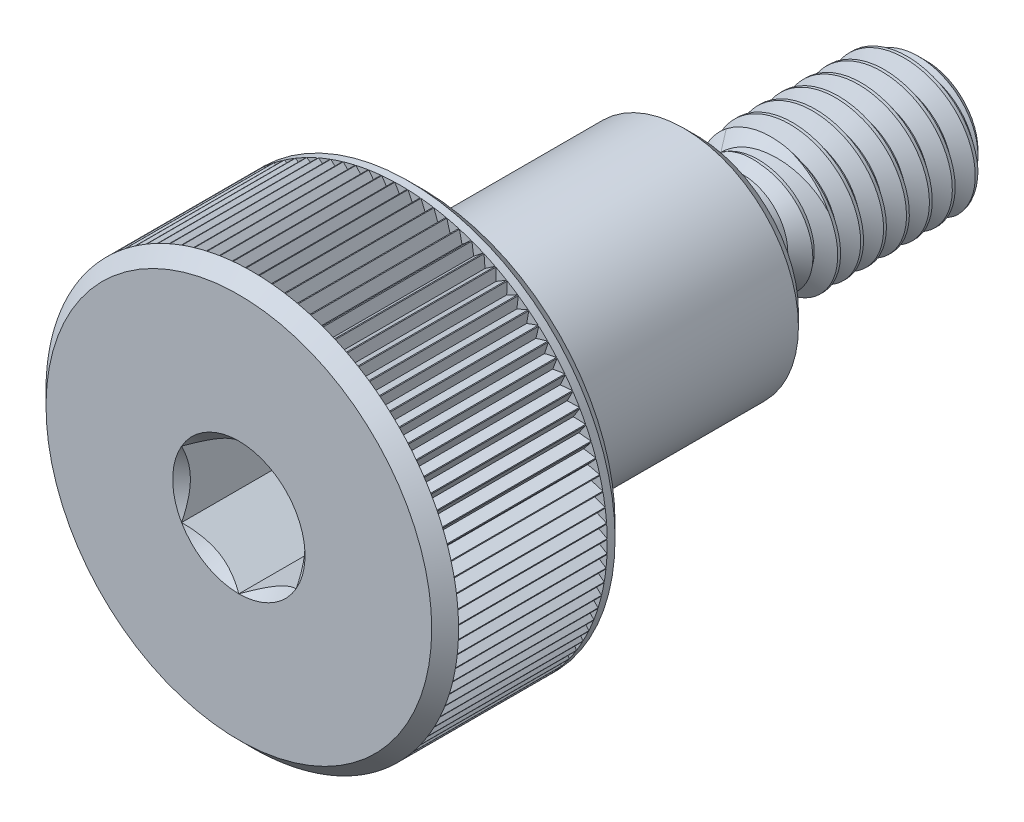
SolidWorks part; units mm, degrees
material "AISI 304"
ref_plane "Front Plane" through (0, 0, 0) normal (0, 0, 1) x (1, 0, 0)
ref_plane "Top Plane" through (0, 0, 0) normal (0, 1, 0) x (1, 0, 0)
ref_plane "Right Plane" through (0, 0, 0) normal (1, 0, 0) x (0, 0, -1)
sketch "Sketch1" plane through (0, 0, 0) normal (1, 0, 0) x (0, 0, -1)
  line L0 (-7.5, 0) -> (7.5, 0) construction
  line L1 (-7.5, -4.5) -> (-7.5, 4.5) construction
  line L2 (-7.5, 4.5) -> (-3.5, 4.5) construction
  line L3 (-3.5, 4.5) -> (-3.5, 2.297) construction
  line L4 (-3.5, 2.297) -> (-2.992, 2.297) construction
  line L5 (-2.992, 2.297) -> (-2.789, 2.5) construction
  line L6 (-2.789, 2.5) -> (2.5, 2.5) construction
  line L7 (7.4687, 1.5541) -> (7.7187, 1.1211) construction
  line L8 (7.7187, 1.1211) -> (7.9688, 1.5541) construction
  line L9 (7.5, -1.5) -> (7.5, 1.5) construction
  line L10 (2.5, 2.5) -> (7.5, 2.5) construction
  line L11 (7.9688, 1.5541) -> (7.4687, 1.5541) construction
  line L12 (7.7188, 1.5541) -> (7.7187, 1.5) construction
  line L13 (7.7187, 1.1211) -> (7.7187, 1.1752) construction
  line L14 (7.75, 1.1752) -> (7.6875, 1.1752) construction
  line L15 (7.9375, 1.5) -> (7.5, 1.5) construction
  line L16 (7.7187, 1.5271) -> (7.9531, 1.5271) construction
  line L17 (7.7187, 1.5271) -> (7.4844, 1.5271) construction
  line L18 (-7.5, 4.2075) -> (-7.2075, 4.5) construction
  line L19 (-3.7925, 4.5) -> (-3.5, 4.2075) construction
  line L20 (7.5, 1.5) -> (2.5, 1.5) construction
  line L21 (7.125, 1.5) -> (7.5, 1.125) construction
  line L22 (4.025, 1.5) -> (3.5, 0.975) construction
  line L23 (3.5, 0.975) -> (2.7625, 0.975) construction
  line L24 (2.5, 1.5) -> (2.5, 1.2375) construction
  line L25 (-5.5, 1.25) -> (-5.5, -1.25) construction
  line L26 (-5.5, -1.25) -> (-7.5, -1.25) construction
  line L27 (-5.5, 1.25) -> (-7.5, 1.25) construction
  line L28 (-7.2075, 0) -> (-3.9633, 0) construction
  arc A0 (2.5, 1.2375) -> (2.7625, 0.975) centre (2.7625, 1.2375) ccw construction
  point P4 (0, 0)
  point P7 (-7.5, 0)
  point P18 (7.5, 0)
  point P25 (5.75, -1.5)
  point P38 (-5.5, 4.5)
  point P45 (-5.5, 0)
  point P46 (3.7625, 1.2375)
  point P48 (-2.992, 0)
  point P51 (-5.5, 0)
  point P52 (2.5, 0)
  dimension "Head Diameter" = 9
  dimension "Head Height" = 4
  dimension "Thread Diameter" = 3
  dimension "Shoulder Diameter" = 5
  dimension "Thread Length" = 5
  dimension "D1" = 0.508
  dimension "D2" = 135
  dimension "D3" = 0.203
  dimension "Shoulder Length" = 6
  dimension "Thread Pitch" = 0.5
  dimension "D4" = 0.0625
  dimension "D5" = 1.75
  dimension "D6" = 0.2925
  dimension "D7" = 0.375
  dimension "D8" = 1.95
  dimension "D9" = 1
  dimension "Drive Size" = 2.5
  dimension "Knurling Length" = 3.2443
sketch "Sketch3" plane through (0, 0, 0) normal (1, 0, 0) x (0, 0, -1)
  line L0 (-7.5, 0) -> (-7.5, 4.2075)
  line L1 (-7.5, -4.5) -> (-7.5, 4.5) construction
  line L2 (-7.5, 4.2075) -> (-7.2075, 4.5)
  line L3 (-7.2075, 4.5) -> (-3.7925, 4.5)
  line L4 (-3.7925, 4.5) -> (-3.5, 4.2075)
  line L5 (-3.5, 4.2075) -> (-3.5, 2.297)
  line L6 (-3.5, 2.297) -> (-2.992, 2.297)
  line L7 (-2.992, 2.297) -> (-2.789, 2.5)
  line L8 (-2.789, 2.5) -> (2.5, 2.5)
  line L9 (2.5, 2.5) -> (2.5, 1.2375)
  line L10 (2.7625, 0.975) -> (3.5, 0.975)
  line L11 (3.5, 0.975) -> (4.025, 1.5)
  line L12 (4.025, 1.5) -> (7.125, 1.5)
  line L13 (7.125, 1.5) -> (7.5, 1.125)
  line L14 (7.5, 1.125) -> (7.5, 0)
  line L15 (7.5, 0) -> (-7.5, 0)
  arc A0 (2.5, 1.2375) -> (2.7625, 0.975) centre (2.7625, 1.2375) ccw construction
  arc A1 (2.5, 1.2375) -> (2.7625, 0.975) centre (2.7625, 1.2375) ccw
revolve "Revolve1" add sketch "Sketch3" angle 360 about L0
sketch "Sketch4" plane through (0, 0, 0) normal (0, 0, 1) x (1, 0, 0)
  line L0 (0, -4.5) -> (0, 4.5) construction
  line L1 (0, 1.4434) -> (-1.25, 0.7217)
  line L2 (-1.25, 0.7217) -> (-1.25, -0.7217)
  line L3 (-1.25, -0.7217) -> (0, -1.4434)
  line L4 (0, -1.4434) -> (1.25, -0.7217)
  line L5 (1.25, -0.7217) -> (1.25, 0.7217)
  line L6 (1.25, 0.7217) -> (0, 1.4434)
  circle A0 centre (0, 0) radius 1.25 construction
extrude "Cut-Extrude1" cut sketch "Sketch4" against normal up to vertex (-5.5 mm away) from vertex up to point (0, 0, 5.5) starting at point (0, 0, 7.5)
sketch "Sketch5" plane through (0, 0, 0) normal (0, 0, 1) x (1, 0, 0)
  line L0 (0, -4.5) -> (0, 4.5) construction
  circle A0 centre (0, 0) radius 1.4434
extrude "Cut-Extrude2" cut sketch "Sketch5" against normal up to vertex (-5.5 mm away) draft 45 from vertex up to point (0, 0, 5.5) starting at point (0, 0, 7.5)
chamfer "Chamfer1" distance 0.2925 angle 45 1 edges at (2.5, 0, -2.5)
sketch "Sketch6" plane through (0, 0, -7.5) normal (0, 0, -1) x (-1, 0, 0)
  circle A0 centre (0, 0) radius 1.5
curve "Helix/Spiral1" pitch 0.5 height 4.75 radius 1.5 centre (0, 0, -7.5) axis (0, 0, 1) start towards (0, 1, 0)
ref_plane "Plane1" through (0, 0, -3.5) normal (0, 0, 1) x (1, 0, 0)
split "Split1" trim tools "Plane1" bodies to split 106 resulting bodies 110 111
sketch "Sketch7" plane through (0, 0, 0) normal (1, 0, 0) x (0, 0, -1)
  line L0 (7.4844, 1.5271) -> (7.6875, 1.1752)
  line L1 (7.6875, 1.1752) -> (7.75, 1.1752)
  line L2 (7.75, 1.1752) -> (7.9531, 1.5271)
  line L3 (7.9531, 1.5271) -> (7.4844, 1.5271)
sweep "Cut-Sweep1" cut profiles "Sketch7" path "Helix/Spiral1" align with end faces yes
combine bodies "Combine1" operation type add bodies to combine 110 107
sketch "Sketch8" plane through (0, 0, 0) normal (0, 0, 1) x (1, 0, 0)
  line L0 (0, 4.5) -> (0, 0) construction
  line L1 (-0.1351, 4.5) -> (0.1351, 4.5)
  line L2 (0.1351, 4.5) -> (0, 4.266)
  line L3 (0, 4.266) -> (-0.1351, 4.5)
  line L4 (-0.1351, 4.5) -> (0, 0) construction
  line L5 (0, 0) -> (0.1351, 4.5) construction
  circle A0 centre (0, 0) radius 4.266 construction
  point P8 (0, 4.5)
  dimension "D1" = 0.234
  dimension "D2" = 3.439
extrude "Cut-Extrude3" cut sketch "Sketch8" against normal up to vertex (-3.9632 mm away) from vertex up to point (0, 0, 3.9633) starting at point (0, 0, 7.2075)
pattern_circular "CirPattern1" count 99 over 360 about axis through (0, 0, 7.5) along (0, 0, -1) of "Cut-Extrude3"
equation "\"D4@Sketch1\"=\"Thread Pitch@Sketch1\"/8"
equation "\"D5@Sketch1\"=\"Thread Pitch@Sketch1\"*3.5"
equation "\"D6@Sketch1\"=\"Head Diameter@Sketch1\"*.0325"
equation "\"D7@Sketch1\"=\"Thread Pitch@Sketch1\"*.75"
equation "\"D8@Sketch1\"=\"Thread Diameter@Sketch1\"*.65"
equation "\"D9@Sketch1\"=\"Thread Length@Sketch1\"*.2"
equation "\"D1@Chamfer1\"=\"D6@Sketch1\""
equation "\"D4@Helix/Spiral1\"=\"Thread Pitch@Sketch1\""
equation "\"D3@Helix/Spiral1\"=\"Thread Length@Sketch1\"*.95"
equation "\"D1@Sketch8\"=\"D6@Sketch1\"*.8"
equation "\"D1@CirPattern1\"=(360/\"D2@Sketch8\")-6"
equation "\"D1\"= \"D11@Sketch1\""
